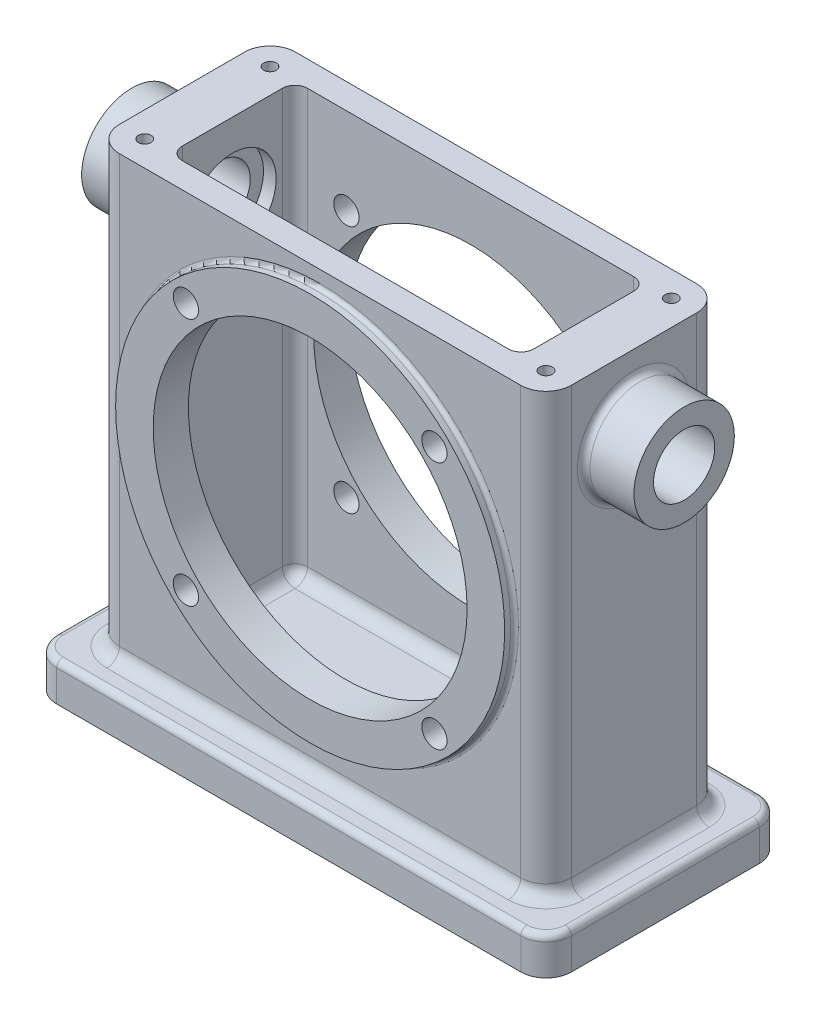
SolidWorks part; units mm, degrees
note: '?' marks a value the reader was unsure of.
ref_plane "Front" through (0, 0, 0) normal (0, 0, 1) x (1, 0, 0)
ref_plane "Top" through (0, 0, 0) normal (0, 1, 0) x (1, 0, 0)
ref_plane "Right" through (0, 0, 0) normal (1, 0, 0) x (0, 0, -1)
sketch "Sketch1" plane through (0, 0, 0) normal (0, 1, 0) x (1, 0, 0)
  line L0 (-65.1, -30.15) -> (65.1, 30.15) construction
  line L1 (-65.1, -30.15) -> (65.1, -30.15)
  line L2 (-65.1, -30.15) -> (-65.1, 30.15)
  line L3 (-65.1, 30.15) -> (65.1, 30.15)
  line L4 (65.1, -30.15) -> (65.1, 30.15)
  dimension "D1" = 130.2
  dimension "D2" = 60.3
extrude "Base-Extrude" add sketch "Sketch1" along normal blind 9.5
sketch "Sketch2" plane through (0, 9.5, 0) normal (0, 1, 0) x (-1, 0, 0)
  line L0 (57.15, 22.25) -> (-57.15, -22.25) construction
  line L1 (57.15, 22.25) -> (-57.15, 22.25)
  line L2 (57.15, 22.25) -> (57.15, -22.25)
  line L3 (57.15, -22.25) -> (-57.15, -22.25)
  line L4 (-57.15, 22.25) -> (-57.15, -22.25)
  dimension "D1" = 114.3
  dimension "D2" = 44.5
extrude "Boss-Extrude1" add sketch "Sketch2" along normal blind 111.1
fillet "Fillet1" radius 6.4 8 edges at (-57.15, 65.05, -22.25) (-57.15, 65.05, 22.25) (57.15, 65.05, 22.25) (57.15, 65.05, -22.25) (-65.1, 4.75, -30.15) (65.1, 4.75, -30.15) (65.1, 4.75, 30.15) (-65.1, 4.75, 30.15)
fillet "Fillet2" radius 1.6 8 edges at (0, 9.5, 30.15) (-65.1, 9.5, 0) (65.1, 9.5, 0) (0, 9.5, -30.15) (-63.2255, 9.5, -28.2755) (63.2255, 9.5, 28.2755) (63.2255, 9.5, -28.2755) (-63.2255, 9.5, 28.2755)
fillet "Fillet3" radius 3.2 8 edges at (-57.15, 9.5, 0) (0, 9.5, -22.25) (57.15, 9.5, 0) (0, 9.5, 22.25) (-55.2755, 9.5, 20.3755) (-55.2755, 9.5, -20.3755) (55.2755, 9.5, 20.3755) (55.2755, 9.5, -20.3755)
sketch "Sketch3" plane through (0, 120.6, 0) normal (0, 1, 0) x (-1, 0, 0)
  line L2 (50.75, 15.85) -> (-50.75, 15.85)
  line L3 (41.25, 15.85) -> (-41.25, 15.85)
  line L5 (-50.75, -15.85) -> (50.75, -15.85)
  line L6 (-41.25, -15.85) -> (41.25, -15.85)
  line L8 (44.45, -15.85) -> (44.45, 15.85)
  line L9 (44.45, -12.65) -> (44.45, 12.65)
  line L11 (-44.45, 15.85) -> (-44.45, -15.85)
  line L12 (-44.45, 12.65) -> (-44.45, -12.65)
  arc A0 (-41.25, 15.85) -> (-44.45, 12.65) centre (-41.25, 12.65) ccw
  arc A1 (44.45, 12.65) -> (41.25, 15.85) centre (41.25, 12.65) ccw
  arc A2 (41.25, -15.85) -> (44.45, -12.65) centre (41.25, -12.65) ccw
  arc A3 (-44.45, -12.65) -> (-41.25, -15.85) centre (-41.25, -12.65) ccw
  dimension "D5" = 3.2
  dimension "D1" = 6.4
  dimension "D2" = 6.4
  dimension "D3" = 12.7
  dimension "D4" = 12.7
extrude "Cut-Extrude1" cut sketch "Sketch3" against normal blind 108
fillet "Fillet4" radius 3.2 8 edges at (43.5127, 12.6, 14.9127) (0, 12.6, 15.85) (-43.5127, 12.6, 14.9127) (-44.45, 12.6, 0) (-43.5127, 12.6, -14.9127) (0, 12.6, -15.85) (43.5127, 12.6, -14.9127) (44.45, 12.6, 0)
sketch "Sketch4" plane through (0, 0, 22.25) normal (0, 0, 1) x (1, 0, 0)
  line L0 (-50.75, 120.6) -> (50.75, 120.6) construction
  line L1 (0, -50) -> (0, 50) construction
  circle A0 centre (0, 67.3) radius 49.2
  dimension "D1" = 98.4
  dimension "D2" = 53.3
extrude "Boss-Extrude2" add sketch "Sketch4" along normal blind 2.5
mirror "Mirror1" about plane through (0, 0, 0) normal (0, 0, 1) of "Boss-Extrude2"
sketch "Sketch5" plane through (0, 0, 24.75) normal (0, 0, 1) x (1, 0, 0)
  circle A0 centre (0, 67.3) radius 39.7
  dimension "D1" = 79.4
extrude "Cut-Extrude2" cut sketch "Sketch5" against normal through all
fillet "Fillet5" radius 1 2 edges at (-49.2, 67.3, 22.25) (49.2, 67.3, -22.25)
sketch "Sketch6" plane through (57.15, 0, 0) normal (1, 0, 0) x (0, 0, -1)
  line L0 (-23.75, 0) -> (23.75, 0) construction
  line L1 (0, 101.6) -> (0, 0) construction
  circle A0 centre (0, 101.6) radius 12.7
  dimension "D1" = 25.4
  dimension "D2" = 101.6
extrude "Boss-Extrude3" add sketch "Sketch6" along normal blind 12.7
sketch "Sketch7" plane through (44.45, 0, 0) normal (-1, 0, 0) x (0, 0, 1)
  circle A0 centre (0, 101.6) radius 7.75
  dimension "D1" = 15.5
extrude "Cut-Extrude3" cut sketch "Sketch7" against normal through all
sketch "Sketch8" plane through (44.45, 0, 0) normal (-1, 0, 0) x (0, 0, 1)
  circle A0 centre (0, 101.6) radius 11.1
  dimension "D1" = 22.2
extrude "Cut-Extrude4" cut sketch "Sketch8" against normal blind 3.2
mirror "Mirror3" about plane through (0, 0, 0) normal (1, 0, 0) of "Cut-Extrude4", "Cut-Extrude3", "Boss-Extrude3"
fillet "Fillet6" radius 1.6 2 edges at (57.15, 101.6, 12.7) (-57.15, 101.6, -12.7)
sketch "Sketch9" plane through (0, 0, 24.75) normal (0, 0, 1) x (1, 0, 0)
  line L0 (31.4309, 98.7309) -> (0, 67.3) construction
  line L1 (0, 67.3) -> (44.45, 67.3) construction
  circle A0 centre (0, 67.3) radius 44.45 construction
  circle A1 centre (31.4309, 98.7309) radius 3.2
  dimension "D1" = 88.9
  dimension "D2" = 6.4
  dimension "D3" = 45
extrude "Cut-Extrude5" cut sketch "Sketch9" against normal through all
ref_axis "CenterLargeHole" through (0, 67.3, -83.0961) along (0, 0, 1)?
pattern_circular "CirPattern1" count 4 over 360 about axis through (0, 67.3, 0) along (0, 0, 1) of "Cut-Extrude5"
sketch "Sketch10" plane through (0, 120.6, 0) normal (0, 1, 0) x (-1, 0, 0)
  line L0 (-41.25, -15.85) -> (41.25, -15.85) construction
  line L1 (41.25, 15.85) -> (-41.25, 15.85) construction
  line L2 (-57.15, 15.85) -> (-57.15, -15.85) construction
  circle A0 centre (-50.75, -15.85) radius 1.6
  circle A1 centre (-50.75, 15.85) radius 1.6
  dimension "D1" = 3.2
  dimension "D2" = 6.4
extrude "Cut-Extrude6" cut sketch "Sketch10" against normal blind 19.1
draft "Draft1" [suppressed] type of draft neutral plane draft angle 1 faces to draft 2 parameters "D1"=1
mirror "Mirror4" about plane through (0, 0, 0) normal (1, 0, 0) of "Draft1", "Cut-Extrude6"
sketch "Sketch11" plane through (0, 120.6, 0) normal (0, 1, 0) x (-1, 0, 0)
  line L0 (-69.85, 12.7) -> (-69.85, -12.7) construction
  line L1 (0, 0) -> (-69.85, 0)
  line L2 (0, 0) -> (0, 30.15)
  line L3 (0, 30.15) -> (-69.85, 30.15)
  line L4 (-69.85, 0) -> (-69.85, 30.15)
  line L5 (-58.7, 30.15) -> (58.7, 30.15) construction
extrude "section cut" [suppressed] cut sketch "Sketch11" against normal through all
